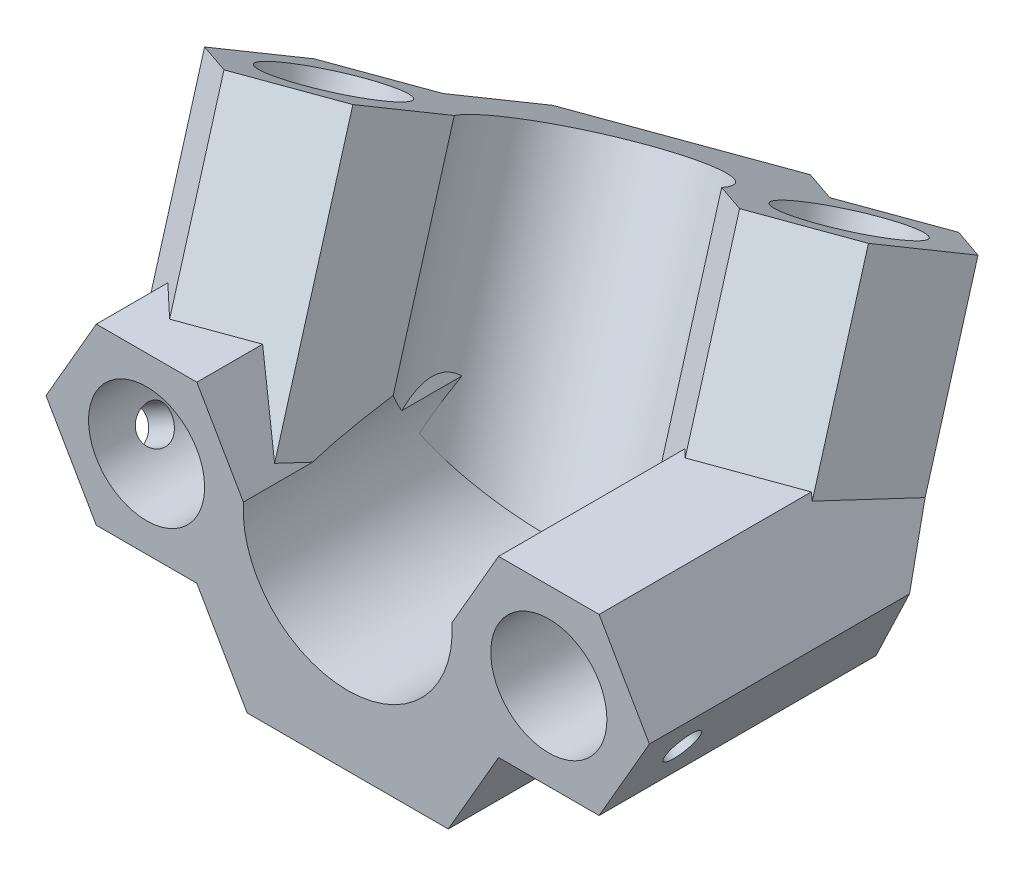
SolidWorks part; units mm, degrees
ref_plane "Front Plane" through (0, 0, 0) normal (0, 0, 1) x (1, 0, 0)
ref_plane "Top Plane" through (0, 0, 0) normal (0, 1, 0) x (1, 0, 0)
ref_plane "Right Plane" through (0, 0, 0) normal (1, 0, 0) x (0, 0, -1)
sketch "Sketch1" plane through (0, 0, 0) normal (0, 1, 0) x (1, 0, 0)
  line L0 (0, 0) -> (0, -10) construction
  line L1 (0, 0) -> (-3.4202, 9.3969) construction
  dimension "D1" = 10
  dimension "D2" = 160
  dimension "D3" = 10
ref_plane "Plane1" through (0, 0, 0) normal (0.9397, 0, -0.342) x (-0.342, 0, -0.9397)
sketch "Sketch2" plane through (0, 0, 0) normal (0.9397, 0, -0.342) x (-0.342, 0, -0.9397)
  line L0 (0, 0) -> (10, 0) construction
  line L1 (0, 0) -> (10, 0) construction
  line L2 (10, 0) -> (10, 17.3205) construction
  line L3 (10, 17.3205) -> (0, 0) construction
  dimension "D1" = 60
  dimension "D2" = 10
sketch "Sketch3" plane through (0, 0, 0) normal (0, 0, 1) x (1, 0, 0)
  line L0 (0, 15) -> (0, -15) construction
  line L1 (12.9904, 7.5) -> (8.6603, 15) construction
  line L2 (8.6603, 15) -> (0, 15) construction
  line L3 (-8.6603, 15) -> (-12.9904, 7.5) construction
  line L4 (-12.9904, -7.5) -> (-8.6603, -15)
  line L5 (-8.6603, -15) -> (8.6603, -15)
  line L6 (8.6603, -15) -> (12.9904, -7.5)
  line L7 (0, 0) -> (17.3205, 0) construction
  line L8 (12.9904, 7.5) -> (10.8253, 3.75) construction
  line L9 (25.9808, 0) -> (21.6506, 7.5)
  line L10 (21.6506, 7.5) -> (12.9904, 7.5)
  line L11 (10.8253, 3.75) -> (8.9827, 0.5584) construction
  line L12 (10.8253, -3.75) -> (12.9904, -7.5) construction
  line L13 (12.9904, -7.5) -> (21.6506, -7.5)
  line L14 (21.6506, -7.5) -> (25.9808, 0)
  line L15 (8.6603, 0) -> (10.8253, -3.75) construction
  line L16 (12.9904, -7.5) -> (13.5705, -6.4952) construction
  line L17 (14.8205, -4.3301) -> (17.3205, 0) construction
  line L18 (13.5705, -6.4952) -> (14.8205, -4.3301) construction
  line L19 (17.3205, 0) -> (14.8205, 4.3301) construction
  line L20 (14.8205, 4.3301) -> (13.5705, 6.4952) construction
  line L21 (13.5705, 6.4952) -> (12.9904, 7.5) construction
  line L22 (-12.9904, -7.5) -> (-21.6506, -7.5)
  line L23 (-21.6506, -7.5) -> (-25.9808, 0)
  line L24 (-25.9808, 0) -> (-21.6506, 7.5)
  line L25 (-21.6506, 7.5) -> (-12.9904, 7.5)
  line L26 (-12.9904, 7.5) -> (-14.8205, 4.3301) construction
  line L27 (-14.8205, 4.3301) -> (-17.3205, 0) construction
  line L28 (-17.3205, 0) -> (-14.8205, -4.3301) construction
  line L29 (-14.8205, -4.3301) -> (-12.9904, -7.5) construction
  line L30 (-17.3205, 7.5) -> (-17.3205, -7.5) construction
  line L31 (-8.9827, 0.5584) -> (-12.9904, 7.5)
  line L32 (8.9827, 0.5584) -> (12.9904, 7.5)
  line L33 (-8.6603, 0) -> (-8.9827, 0.5584) construction
  line L34 (0, 15) -> (-8.6603, 15) construction
  line L35 (8.9827, 0.5584) -> (8.6603, 0) construction
  line L36 (8.6603, 0) -> (8.9827, 0.5584) construction
  circle A0 centre (0, 0) radius 15 construction
  circle A1 centre (17.3205, 0) radius 5
  circle A2 centre (17.3205, 0) radius 7.5 construction
  circle A3 centre (-17.3205, 0) radius 5
  arc A4 (-8.9827, 0.5584) -> (8.9827, 0.5584) centre (0, 0) ccw
  arc A5 (0, 9) -> (-8.9827, 0.5584) centre (0, 0) ccw construction
  arc A6 (8.9827, 0.5584) -> (0, 9) centre (0, 0) ccw construction
  dimension "D2" = 10
  dimension "D4" = 18
  dimension "D1" = 30
  dimension "D3" = 15
extrude "Boss-Extrude1" add sketch "Sketch3" along normal blind 15
ref_plane "Plane2" through (-3.4202, 17.3205, -9.3969) normal (0.171, -0.866, 0.4698) x (-0.9849, -0.1641, 0.056)
sketch "Sketch25" plane through (0, 0, 0) normal (0, 0, -1) x (-1, 0, 0)
  line L0 (-8.9827, 0.5584) -> (-12.9904, 7.5)
  line L1 (-12.9904, 7.5) -> (-21.6506, 7.5)
  line L2 (-21.6506, 7.5) -> (-25.9808, 0)
  line L3 (-25.9808, 0) -> (-21.6506, -7.5)
  line L4 (-21.6506, -7.5) -> (-12.9904, -7.5)
  line L5 (-12.9904, -7.5) -> (-8.6603, -15)
  line L6 (-8.6603, -15) -> (8.6603, -15)
  line L7 (8.6603, -15) -> (12.9904, -7.5)
  line L8 (12.9904, -7.5) -> (21.6506, -7.5)
  line L9 (21.6506, -7.5) -> (25.9808, 0)
  line L10 (25.9808, 0) -> (21.6506, 7.5)
  line L11 (21.6506, 7.5) -> (12.9904, 7.5)
  line L12 (12.9904, 7.5) -> (8.9827, 0.5584)
  arc A0 (-8.9827, 0.5584) -> (8.9827, 0.5584) centre (0, 0) ccw
  arc A1 (-8.9827, 0.5584) -> (8.9827, 0.5584) centre (0, 0) ccw construction
  arc A2 (8.9827, 0.5584) -> (-8.9827, 0.5584) centre (0, 0) ccw construction
sketch "Sketch11" plane through (-3.4202, 17.3205, -9.3969) normal (0.171, -0.866, 0.4698) x (-0.9849, -0.1641, 0.056)
  line L0 (-4.9224, -14.1693) -> (4.9224, 14.1693) construction
  line L7 (13.1031, 11.3274) -> (-3.2583, 17.0113)
  line L20 (-3.2583, 17.0113) -> (-9.8098, 11.3476)
  line L21 (-14.7322, -2.8218) -> (-13.1031, -11.3274) construction
  line L22 (-4.9224, -14.1693) -> (3.2583, -17.0113) construction
  line L23 (3.2583, -17.0113) -> (9.8098, -11.3476) construction
  line L24 (16.3613, -5.6839) -> (15.4208, -0.7732) construction
  line L25 (2.8419, 8.1807) -> (0, 0) construction
  line L26 (-16.3613, 5.6839) -> (16.3613, -5.6839) construction
  line L27 (14.7322, 2.8218) -> (11.4564, -0.0101) construction
  line L28 (-9.8098, 11.3476) -> (-17.9905, 14.1895)
  line L35 (-17.9905, 14.1895) -> (-24.542, 8.5258)
  line L42 (-24.542, 8.5258) -> (-22.9129, 0.0202)
  line L43 (-22.9129, 0.0202) -> (-14.7322, -2.8218)
  line L44 (-14.7322, -2.8218) -> (-8.6685, 2.4202)
  line L45 (-8.302, 3.4752) -> (-8.9952, 7.0948) construction
  line L46 (24.542, -8.5258) -> (22.9129, -0.0202)
  line L47 (22.9129, -0.0202) -> (14.7322, 2.8218)
  line L48 (8.6685, -2.4202) -> (8.1807, -2.8419) construction
  line L49 (8.302, -3.4752) -> (9.8098, -11.3476)
  line L50 (9.8098, -11.3476) -> (17.9905, -14.1895)
  line L51 (17.9905, -14.1895) -> (24.542, -8.5258)
  line L52 (11.4564, -0.0101) -> (8.6685, -2.4202) construction
  line L53 (8.1807, -2.8419) -> (8.302, -3.4752) construction
  line L54 (14.9505, 1.6822) -> (14.7322, 2.8218) construction
  line L55 (14.7322, 2.8218) -> (13.1031, 11.3274)
  line L56 (15.4208, -0.7732) -> (14.9505, 1.6822) construction
  line L57 (12.5788, -8.9538) -> (16.3613, -5.6839) construction
  line L58 (10.6875, -10.5888) -> (12.5788, -8.9538) construction
  line L59 (9.8098, -11.3476) -> (10.6875, -10.5888) construction
  line L60 (-8.9952, 7.0948) -> (-9.8098, 11.3476) construction
  line L61 (-10.6875, 10.5888) -> (-12.5788, 8.9538) construction
  line L62 (-12.5788, 8.9538) -> (-16.3613, 5.6839) construction
  line L63 (-16.3613, 5.6839) -> (-15.4208, 0.7732) construction
  line L64 (-9.8098, 11.3476) -> (-10.6875, 10.5888) construction
  line L65 (-15.4208, 0.7732) -> (-14.9505, -1.6822) construction
  line L66 (-14.9505, -1.6822) -> (-14.7322, -2.8218) construction
  line L67 (-8.6685, 2.4202) -> (-8.1807, 2.8419) construction
  line L68 (-8.1807, 2.8419) -> (-8.302, 3.4752) construction
  line L69 (-13.1031, -11.3274) -> (-4.9224, -14.1693) construction
  circle A0 centre (0, 0) radius 15 construction
  circle A2 centre (-16.3613, 5.6839) radius 7.5 construction
  circle A4 centre (-16.3613, 5.6839) radius 5
  circle A5 centre (16.3613, -5.6839) radius 7.5 construction
  circle A6 centre (16.3613, -5.6839) radius 5
  arc A7 (8.302, -3.4752) -> (-8.6685, 2.4202) centre (0, 0) ccw
  arc A8 (-2.9534, -8.5016) -> (8.302, -3.4752) centre (0, 0) ccw construction
  arc A9 (-8.6685, 2.4202) -> (-2.9534, -8.5016) centre (0, 0) ccw construction
  dimension "D2" = 15
  dimension "D4" = 15
  dimension "D3" = 10
  dimension "D5" = 10
  dimension "D6" = 18
  dimension "D1" = 30
extrude "Boss-Extrude6" add sketch "Sketch11" along normal up to surface (32.9904 mm away) up to face at (0, -15, 7.5)
sketch "Sketch22" plane through (0, 0, 15) normal (0, 0, 1) x (1, 0, 0)
  line L0 (8.6603, -15) -> (-8.6603, -15)
  circle A0 centre (-17.3205, 0) radius 5
  arc A1 (-12.6933, -1.8945) -> (-18.3492, 4.893) centre (-17.3205, 0) ccw construction
  circle A2 centre (17.3205, 0) radius 5
  circle A3 centre (17.3205, 0) radius 5 construction
  circle A4 centre (0, 0) radius 9
  arc A5 (-8.9827, 0.5584) -> (8.9827, 0.5584) centre (0, 0) ccw construction
  arc M23 (8.9827, 0.5584) -> (-8.9827, 0.5584) centre (0, 0) cw
extrude "Cut-Extrude5" cut sketch "Sketch22" against normal up to surface (15 mm away) contours A4 M23 | A0 | A2 region at (0, 0, 15) up to face at (-20.2004, -3.4849, 0)
sketch "Sketch23" plane through (0, 0, 0) normal (0, 1, 0) x (1, 0, 0)
  line L0 (25.9808, -15) -> (25.9808, 0) construction
  line L1 (-25.9808, -15) -> (25.9808, -15)
  line L2 (-25.9808, -15) -> (-25.9808, -23.6809)
  line L3 (-25.9808, -23.6809) -> (25.9808, -23.6809)
  line L4 (25.9808, -15) -> (25.9808, -23.6809)
extrude "Cut-Extrude6" cut sketch "Sketch23" against normal through all both and the other way through all
sketch "Sketch24" plane through (0, 0, 15) normal (0, 0, 1) x (1, 0, 0)
  line L0 (-25.9808, 0) -> (-21.6506, -7.5)
  line L1 (-21.6506, -7.5) -> (-12.9904, -7.5)
  line L2 (-12.9904, -7.5) -> (-8.6603, -15)
  line L3 (-8.6603, -15) -> (-21.219, -15)
  line L4 (-21.219, -15) -> (-25.9808, 0)
  line L5 (8.6603, -15) -> (12.9904, -7.5)
  line L6 (12.9904, -7.5) -> (21.6506, -7.5)
  line L7 (21.6506, -7.5) -> (25.9808, 0)
  line L8 (25.9808, 0) -> (27.3759, -15)
  line L9 (27.3759, -15) -> (8.6603, -15)
extrude "Cut-Extrude7" cut sketch "Sketch24" against normal through all both and the other way through all
extrude "Boss-Extrude7" add sketch "Sketch25" along normal up to surface (22.0446 mm away) up to face at (-6.3157, -3.7874, -13.8064)
sketch "Sketch26" plane through (-3.4202, 17.3205, -9.3969) normal (-0.171, 0.866, -0.4698) x (0.9853, 0.1503, -0.0815)
  line L0 (-12.769, 11.7026) -> (-14.6442, 3.2478)
  line L1 (-14.6442, 3.2478) -> (-25.6176, -0.2111)
  line L2 (-26.8213, -13.1846) -> (-24.8661, 7.8896) construction
  line L3 (-25.6176, -0.2111) -> (-24.8661, 7.8896)
  line L4 (-24.8661, 7.8896) -> (-12.769, 11.7026)
  line L5 (3.7502, 16.9096) -> (10.1348, 11.0583)
  line L6 (10.1348, 11.0583) -> (18.3944, 13.6618)
  line L7 (18.3944, 13.6618) -> (26.2017, 6.5066)
  line L8 (24.3748, -13.1846) -> (27.8723, 24.5131) construction
  line L9 (26.2017, 6.5066) -> (27.8723, 24.5131)
  line L10 (27.8723, 24.5131) -> (3.7502, 16.9096)
extrude "Cut-Extrude8" cut sketch "Sketch26" against normal through all both and the other way through all
sketch "Sketch27" plane through (-19.4856, -11.25, 0) normal (-0.866, -0.5, 0) x (0, 0, 1)
  line L0 (15, 8.6603) -> (1.7562, 8.6603) construction
  line L1 (15, 12.9904) -> (15, 4.3301) construction
  line L2 (0.2402, 12.9904) -> (3.2722, 4.3301) construction
  line L3 (10, 12.9904) -> (10, 4.3301) construction
  line L4 (15, 12.9904) -> (0.2402, 12.9904) construction
  line L5 (15, 4.3301) -> (3.2722, 4.3301) construction
  circle A0 centre (10, 8.6603) radius 1.5
  dimension "D1" = 3
  dimension "D2" = 5
extrude "Cut-Extrude9" cut sketch "Sketch27" against normal up to surface and the other way through all up to face at (-17.3205, 0, 0.3293)
sketch "Sketch28" plane through (19.4856, -11.25, 0) normal (0.866, -0.5, 0) x (0, 0, -1)
  line L0 (-15, 8.6603) -> (8.119, 8.6603) construction
  line L1 (-15, 4.3301) -> (-15, 12.9904) construction
  line L2 (8.8355, 4.3301) -> (7.4025, 12.9904) construction
  circle A0 centre (-10, 8.6603) radius 1.5
  dimension "D1" = 3
  dimension "D2" = 5
extrude "Cut-Extrude10" cut sketch "Sketch28" against normal up to surface (2.7303 mm away) up to face at (22.3205, 0, 0)
sketch "Sketch29" plane through (-21.6427, -5.625, -2.4908) normal (-0.9619, -0.25, -0.1107) x (-0.1071, -0.0278, 0.9939)
  line L0 (-1.8237, 21.7181) -> (5.114, 8.7865) construction
  line L1 (1.992, 23.7651) -> (-5.6394, 19.671) construction
  line L2 (-0.1152, 9.3741) -> (10.3432, 8.1988) construction
  circle A0 centre (0.5401, 17.3121) radius 1.5
  dimension "D1" = 3
  dimension "D2" = 5
extrude "Cut-Extrude11" cut sketch "Sketch29" against normal up to surface (2.5505 mm away) contours A0 up to face at (-19.6962, 14.9362, -7.8678)
sketch "Sketch30" plane through (14.9782, -5.625, -15.8197) normal (0.6657, -0.25, -0.7031) x (-0.7462, -0.223, -0.6272)
  line L0 (-3.8464, 21.4524) -> (-9.6694, -3.2805) construction
  line L1 (0.3685, 20.4601) -> (-8.0613, 22.4447) construction
  line L2 (-8.9416, -4.1065) -> (-14.7444, 2.48) construction
  circle A0 centre (-4.9923, 16.5855) radius 1.5
  dimension "D1" = 3
  dimension "D2" = 5
extrude "Cut-Extrude12" cut sketch "Sketch30" against normal up to surface (2.6834 mm away) up to face at (12.8558, 14.9362, -19.7158)
sketch "Sketch31" plane through (-4.443, -7.5, -12.207) normal (-0.2962, -0.5, -0.8138) x (-0.9551, 0.1551, 0.2524)
  line L0 (3.5809, 19.6768) -> (-1.5506, -8.5203) construction
  line L1 (12.1012, 18.1262) -> (-4.9394, 21.2274) construction
  line L2 (-10.0709, -6.9697) -> (4.4154, -9.606) construction
  line L3 (-4.0102, -8.0727) -> (-2.5778, -0.202)
  line L4 (-2.5778, -0.202) -> (2.3414, -1.0972)
  line L5 (2.3414, -1.0972) -> (0.909, -8.9679)
  line L6 (0.909, -8.9679) -> (-4.0102, -8.0727)
  point P8 (-0.1182, -0.6496)
  dimension "D1" = 5
  dimension "D2" = 8
extrude "Boss-Extrude8" add sketch "Sketch31" along normal blind 5
sketch "Sketch32" plane through (2.3492, 0, -0.8551) normal (0.9397, 0, -0.342) x (-0.342, 0, -0.9397)
  line L0 (14.8253, -9.3218) -> (10.8253, -16.25) construction
  line L1 (16.9904, -10.5718) -> (12.6603, -8.0718) construction
  line L2 (12.9904, -17.5) -> (8.6603, -15) construction
  circle A0 centre (12.8253, -12.7859) radius 1.5
  dimension "D1" = 3
extrude "Cut-Extrude13" cut sketch "Sketch32" against normal through all
fillet "Fillet1" radius 3 1 edges at (-5.8111, -10.5718, -15.9657) type face fillet first side face at (-5.127, -14.0359, -14.0864) second side face at (-5.0706, -9.3218, -13.9312)
fillet "Fillet2" radius 3 1 edges at (-4.443, -17.5, -12.207) type face fillet first side face at (-4.8705, -15.3349, -13.3816) second side face at (-3.7025, -16.25, -10.1725)
sketch "Sketch33" plane through (-4.443, -7.5, -12.207) normal (-0.2962, -0.5, -0.8138) x (-0.9551, 0.1551, 0.2524)
  line L0 (-1.5506, -8.5203) -> (20.9683, 115.2197) construction
  line L1 (-4.0102, -8.0727) -> (0.909, -8.9679) construction
  line L2 (12.1012, 18.1262) -> (-4.9394, 21.2274) construction
